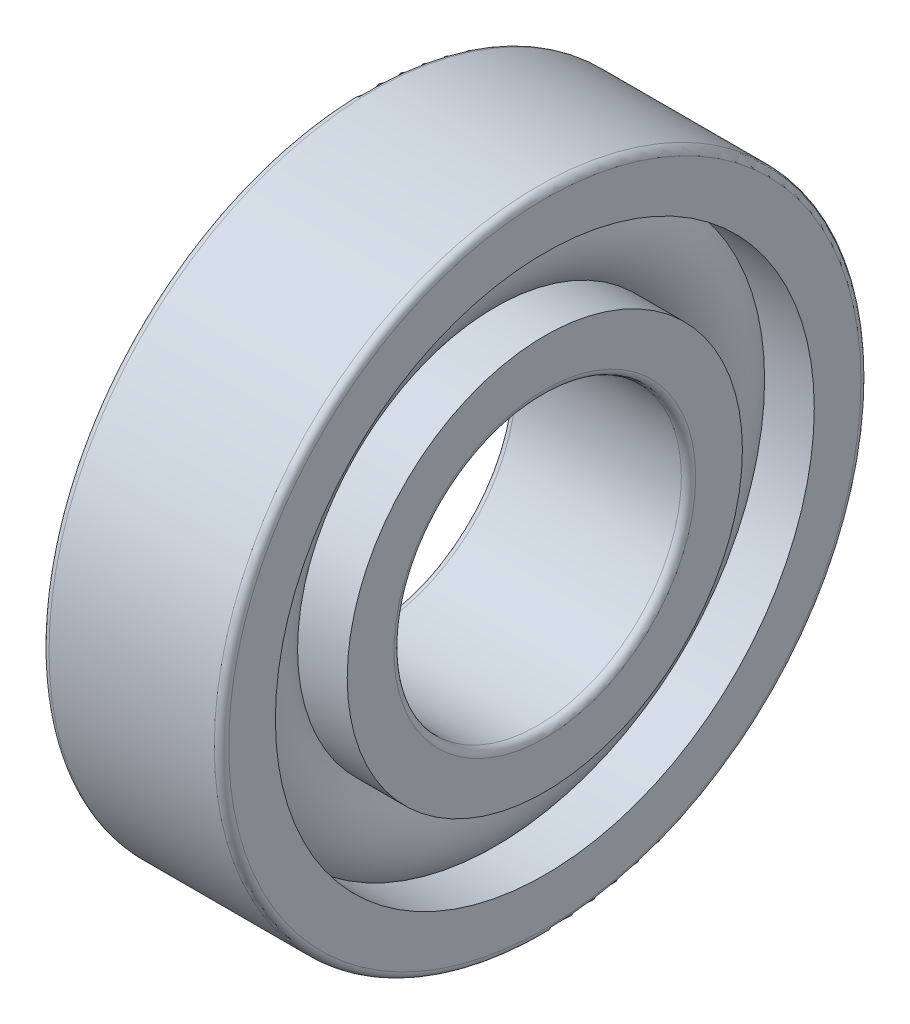
SolidWorks part; units mm, degrees
ref_plane "Plane1" through (0, 0, 0) normal (0, 0, 1) x (1, 0, 0)
ref_plane "Plane2" through (0, 0, 0) normal (0, 1, 0) x (1, 0, 0)
ref_plane "Plane3" through (0, 0, 0) normal (1, 0, 0) x (0, 0, -1)
sketch "Clipboard" plane through (0, 0, 0) normal (0, 0, 1) x (1, 0, 0)
  line L0 (-10, 0) -> (10, 0) construction
  line L1 (0, 0) -> (22.3471, -0.7804)
  line L2 (0, 0) -> (3.248, 0.1134)
  line L3 (0, 0) -> (22.3471, -0.7804)
  line L4 (0, 0) -> (-22.3573, -0.3902)
  dimension "BallCLRad" = 3.25
  dimension "Count" = 2
  dimension "Show_count" = 2
  dimension "Max_count" = 2
  dimension "Min_count" = 1
sketch "CagSpiSke" plane through (0, 0, 0) normal (0, 0, 1) x (1, 0, 0)
  line L0 (0.075, 3.125) -> (0.075, 3.375)
  line L1 (0.075, 3.375) -> (-0.075, 3.375)
  line L2 (-0.075, 3.375) -> (-0.075, 3.125)
  line L3 (-0.075, 3.125) -> (0.075, 3.125)
  line L4 (-20.6375, 0) -> (20.6375, 0) construction
  line L5 (0, 0) -> (0, 23.7692) construction
  dimension "Thickness" = 0.15
  dimension "OD" = 6.75
  dimension "ID" = 6.25
revolve "CageSpine" add sketch "CagSpiSke" angle 0.001 about L4 reverse direction yes
ref_axis "Axis1" through (-50, 0, 0) along (1, 0, 0)
sketch "CagBalSke" plane through (0, 0, 0) normal (0, 0, 1) x (1, 0, 0)
  line L0 (-0.825, 3.25) -> (0.825, 3.25)
  line L1 (-1.905, 3.25) -> (1.905, 3.25) construction
  line L2 (-10, 0) -> (10, 0) construction
  line L3 (0, 0) -> (0, 24) construction
  arc A0 (0.825, 3.25) -> (-0.825, 3.25) centre (0, 3.25) cw
  dimension "CageWallOD" = 1.65
  dimension "BallCLRad" = 3.25
revolve "CageBall" [suppressed] add sketch "CagBalSke" angle 360 about L1 reverse direction yes
pattern_circular "CageBalls" [suppressed] count 2 every 180 about axis through (-50, 0, 0) along (1, 0, 0)
sketch "CagTrmODSke" plane through (0, 0, 0) normal (0, 0, 1) x (1, 0, 0)
  line L0 (0.826, 3.375) -> (0.826, 4.076)
  line L1 (0.826, 4.076) -> (-0.826, 4.076)
  line L2 (-0.826, 4.076) -> (-0.826, 3.375)
  line L3 (-0.826, 3.375) -> (0.826, 3.375)
  line L4 (-20.6375, 0) -> (20.6375, 0) construction
  line L5 (0, 0) -> (0, 25) construction
  dimension "Width" = 1.652
  dimension "ID" = 6.75
  dimension "OD" = 8.152
revolve "CageTrimOD" [suppressed] cut sketch "CagTrmODSke" angle 360 about L4 reverse direction yes
sketch "CagTrmIDSke" plane through (0, 0, 0) normal (0, 0, 1) x (1, 0, 0)
  line L0 (0.826, 2.426) -> (0.826, 3.125)
  line L1 (0.826, 3.125) -> (-0.826, 3.125)
  line L2 (-0.826, 3.125) -> (-0.826, 2.426)
  line L3 (-0.826, 2.426) -> (0.826, 2.426)
  line L4 (-20.6375, 0) -> (20.6375, 0) construction
  line L5 (0, 0) -> (0, 25) construction
  dimension "ID" = 4.852
  dimension "OD" = 6.25
  dimension "Width" = 1.652
revolve "CageTrimID" [suppressed] cut sketch "CagTrmIDSke" angle 360 about L4 reverse direction yes
sketch "BalSimSke" plane through (0, 0, 0) normal (0, 0, 1) x (1, 0, 0)
  line L0 (-10, 0) -> (10, 0) construction
  line L1 (-10, 3.25) -> (10, 3.25) construction
  line L2 (0, 0) -> (0, 23) construction
  circle A0 centre (0, 3.25) radius 0.75
  dimension "Ball_diameter" = 1.5
  dimension "BallCLRad" = 3.25
revolve "BallsSimplified" add sketch "BalSimSke" angle 360 about L0
sketch "BalDetSke" plane through (0, 0, 0) normal (0, 0, 1) x (1, 0, 0)
  line L0 (-0.75, 3.25) -> (0.75, 3.25)
  line L1 (-1.905, 3.25) -> (1.905, 3.25) construction
  line L2 (0, 0) -> (0, 25) construction
  arc A0 (0.75, 3.25) -> (-0.75, 3.25) centre (0, 3.25) cw
  dimension "Ball_diameter" = 1.5
  dimension "BallCLRad" = 3.25
revolve "BallDetailed" [suppressed] add sketch "BalDetSke" angle 360 about L1 reverse direction yes
sketch "InnRacSke" plane through (0, 0, 0) normal (0, 0, 1) x (1, 0, 0)
  line L0 (-0.525, 2.75) -> (-1.25, 2.75)
  line L1 (-1.25, 2.75) -> (-1.25, 2.1)
  line L2 (-1.15, 2) -> (1.15, 2)
  line L3 (1.25, 2.1) -> (1.25, 2.75)
  line L4 (1.25, 2.75) -> (0.525, 2.75)
  line L5 (-20.6375, 0) -> (20.6375, 0) construction
  line L6 (0, 0) -> (0, 30) construction
  arc A0 (-1.25, 2.1) -> (-1.15, 2) centre (-1.15, 2.1) ccw
  arc A1 (1.15, 2) -> (1.25, 2.1) centre (1.15, 2.1) ccw
  arc A2 (0.525, 2.75) -> (-0.525, 2.75) centre (0, 3.25) cw
  dimension "Fillet_radius" = 0.1
  dimension "Ball_diameter" = 1.45
  dimension "ID" = 4
  dimension "OD" = 5.5
  dimension "Width" = 2.5
  dimension "BallCLRad" = 3.25
revolve "InnerRace" add sketch "InnRacSke" angle 360 about L5 reverse direction yes
sketch "OutRacSke" plane through (0, 0, 0) normal (0, 0, 1) x (1, 0, 0)
  line L0 (-0.525, 3.75) -> (-1.25, 3.75)
  line L1 (-1.25, 3.75) -> (-1.25, 4.4)
  line L2 (-1.15, 4.5) -> (1.15, 4.5)
  line L3 (1.25, 4.4) -> (1.25, 3.75)
  line L4 (1.25, 3.75) -> (0.525, 3.75)
  line L5 (-20.6375, 0) -> (20.6375, 0) construction
  line L6 (0, 0) -> (0, 30) construction
  arc A0 (-1.25, 4.4) -> (-1.15, 4.5) centre (-1.15, 4.4) cw
  arc A1 (1.15, 4.5) -> (1.25, 4.4) centre (1.15, 4.4) cw
  arc A2 (0.525, 3.75) -> (-0.525, 3.75) centre (0, 3.25) ccw
  dimension "Fillet_radius" = 0.1
  dimension "Ball_diameter" = 1.45
  dimension "OD" = 9
  dimension "ID" = 7.5
  dimension "Width" = 2.5
  dimension "BallCLRad" = 3.25
revolve "OuterRace" add sketch "OutRacSke" angle 360 about L5 reverse direction yes
pattern_circular "BallsDetailed" [suppressed] count 2 every 180 about axis through (-50, 0, 0) along (1, 0, 0)
equation "\"BallCLRad@Clipboard\" = ( \"OD@OutRacSke\" + \"ID@InnRacSke\" ) / 4"
equation "\"BallCLRad@BalSimSke\" = \"BallCLRad@Clipboard\""
equation "\"BallCLRad@BalDetSke\" = \"BallCLRad@Clipboard\""
equation "\"BallCLRad@InnRacSke\" = \"BallCLRad@Clipboard\""
equation "\"BallCLRad@OutRacSke\" = \"BallCLRad@Clipboard\""
equation "\"Ball_diameter@InnRacSke\" = \"Ball_diameter@BalDetSke\" - 0.05"
equation "\"Ball_diameter@OutRacSke\" = \"Ball_diameter@BalDetSke\" - 0.05"
equation "\"Ball_diameter@BalSimSke\" = \"Ball_diameter@BalDetSke\""
equation "\"Width@OutRacSke\" = \"Width@InnRacSke\""
equation "\"Fillet_radius@OutRacSke\" = \"Fillet_radius@InnRacSke\""
equation "\"Max_count@Clipboard\" = int( 3.14159265 / atn(( \"Ball_diameter@BalDetSke\" / 2) / sqr( \"BallCLRad@Clipboard\"  *  \"BallCLRad@Clipboard\" - ( \"Ball_diameter@BalDetSke\" / 2) *  ( \"Ball_diameter@BalDetSke\" / 2))))"
equation "\"Max_count@Clipboard\" = ((sgn( \"Max_count@Clipboard\" - \"Count@Clipboard\" )-1)*( \"Max_count@Clipboard\" - \"Count@Clipboard\" ))/-2+ \"Count@Clipboard\""
equation "\"Count@BallsDetailed\" = int( \"Show_count@Clipboard\" ) "
equation "\"Count@BallsDetailed\" = ((sgn( \"Count@BallsDetailed\" - \"Max_count@Clipboard\" )-1)*( \"Count@BallsDetailed\" - \"Max_count@Clipboard\" ))/-2+ \"Max_count@Clipboard\""
equation "\"Count@BallsDetailed\" = ((sgn( \"Count@BallsDetailed\" - \"Min_count@Clipboard\" )+1)*( \"Count@BallsDetailed\" - \"Min_count@Clipboard\"))/2 +\"Min_count@Clipboard\""
equation "\"Angle@BallsDetailed\" = 360.0 / \"Max_count@Clipboard\""
equation "\"BallCLRad@CagBalSke\" = \"BallCLRad@Clipboard\""
equation "\"Count@CageBalls\" = \"Count@BallsDetailed\""
equation "\"Angle@CageBalls\" = \"Angle@BallsDetailed\""
equation "\"Angle@CageSpine\" =  \"Angle@CageBalls\" * ( \"Count@CageBalls\" -1 + int( \"Count@CageBalls\" / \"Max_count@Clipboard\" ) )  + 0.001 -  int( \"Count@CageBalls\" / \"Max_count@Clipboard\" ) * 0.001"
equation "\"Angle@CageSpine\" =  \"Angle@CageSpine\" * int( \"Min_count@Clipboard\" / 2) + int(1 / \"Min_count@Clipboard\")  * 0.001"
equation "\"CageWallOD@CagBalSke\" =  \"Ball_diameter@BalDetSke\" * 1.1"
equation "\"Thickness@CagSpiSke\" =  \"Ball_diameter@BalDetSke\" * 0.1"
equation "\"OD@CagTrmODSke\" = \"BallCLRad@Clipboard\" * 2 + \"CageWallOD@CagBalSke\" + 0.002"
equation "\"ID@CagTrmODSke\" = \"BallCLRad@Clipboard\" * 2 + \"Ball_diameter@BalDetSke\" / 6"
equation "\"OD@CagTrmIDSke\" = \"BallCLRad@Clipboard\" * 2 - \"Ball_diameter@BalDetSke\" / 6"
equation "\"ID@CagTrmIDSke\" = \"BallCLRad@Clipboard\" * 2 - \"CageWallOD@CagBalSke\" + 0.002"
equation "\"OD@CagSpiSke\" = \"ID@CagTrmODSke\""
equation "\"ID@CagSpiSke\" = \"OD@CagTrmIDSke\""
equation "\"Width@CagTrmODSke\" = \"CageWallOD@CagBalSke\" + 0.002"
equation "\"Width@CagTrmIDSke\" = \"CageWallOD@CagBalSke\" + 0.002"
